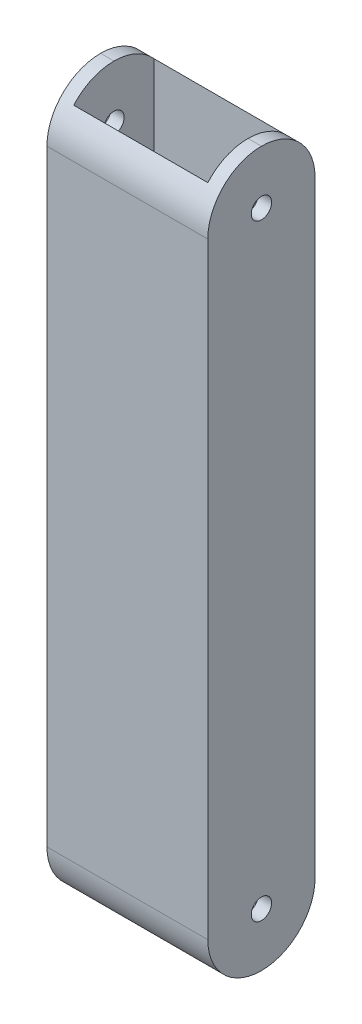
SolidWorks part; units mm, degrees
material "6061-T6 (SS)"
ref_plane "Front Plane" through (0, 0, 0) normal (0, 0, 1) x (1, 0, 0)
ref_plane "Top Plane" through (0, 0, 0) normal (0, 1, 0) x (1, 0, 0)
ref_plane "Right Plane" through (0, 0, 0) normal (1, 0, 0) x (0, 0, -1)
sketch "Sketch1" plane through (0, 0, 0) normal (0, 1, 0) x (1, 0, 0)
  line L1 (-19.05, -12.7) -> (19.05, -12.7)
  line L2 (-19.05, -12.7) -> (-19.05, 12.7)
  line L3 (-19.05, 12.7) -> (19.05, 12.7)
  line L4 (19.05, -12.7) -> (19.05, 12.7)
  line L5 (-19.05, -12.7) -> (19.05, 12.7) construction
  line L6 (-19.05, 12.7) -> (19.05, -12.7) construction
  line L7 (-15.875, -9.525) -> (15.875, -9.525)
  line L8 (-15.875, -9.525) -> (-15.875, 9.525)
  line L9 (-15.875, 9.525) -> (15.875, 9.525)
  line L10 (15.875, -9.525) -> (15.875, 9.525)
  line L11 (-15.875, -9.525) -> (15.875, 9.525) construction
  line L12 (-15.875, 9.525) -> (15.875, -9.525) construction
  point P0 (0, 0)
  point P6 (0, 0)
  dimension "D1" = 38.1
  dimension "D2" = 25.4
  dimension "D3" = 3.175
  dimension "D4" = 3.175
extrude "Boss-Extrude1" add sketch "Sketch1" along normal blind 169.1066
sketch "Sketch2" plane through (19.05, 0, 0) normal (1, 0, 0) x (0, 0, -1)
  line L0 (0, 169.1066) -> (0, 156.4066) construction
  line L1 (-12.7, 169.1066) -> (12.7, 169.1066) construction
  line L2 (0, 0) -> (0, 12.7) construction
  line L3 (-12.7, 0) -> (12.7, 0) construction
  circle A0 centre (0, 156.4066) radius 2.413
  circle A1 centre (0, 12.7) radius 2.413
  dimension "D2" = 4.826
  dimension "D4" = 4.826
  dimension "D1" = 12.7
  dimension "D3" = 12.7
extrude "Cut-Extrude1" cut sketch "Sketch2" against normal through all both and the other way through all
fillet "Fillet7" radius 12.7 4 edges at (0, 169.1066, -12.7) (0, 0, 12.7) (0, 0, -12.7) (0, 169.1066, 12.7)
